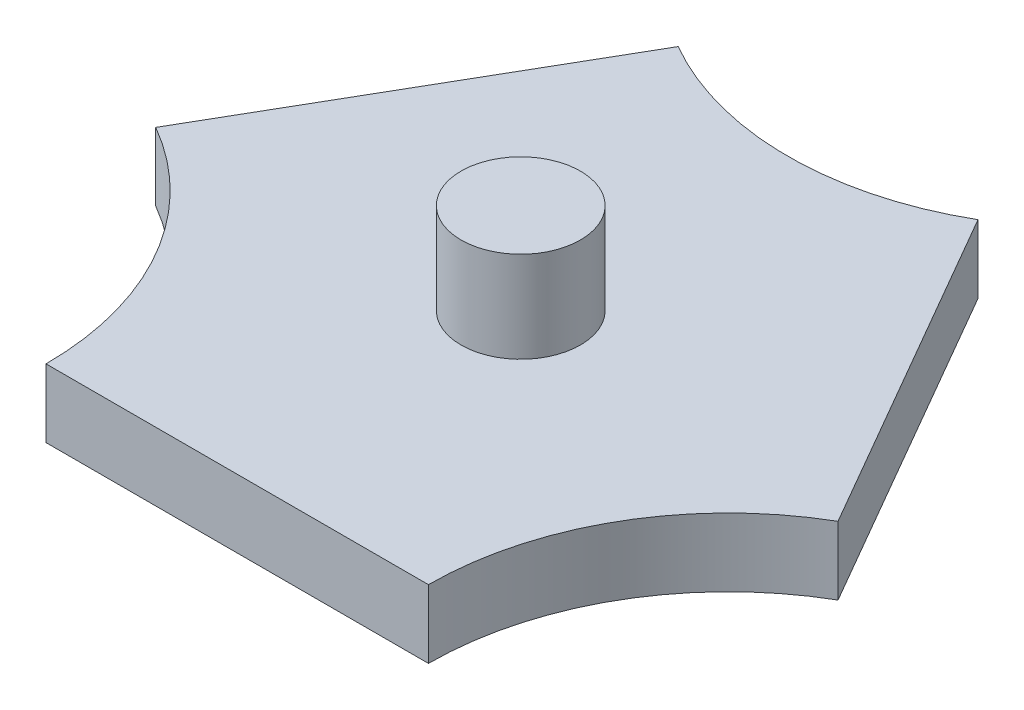
SolidWorks part; units mm, degrees
ref_plane "Front Plane" through (0, 0, 0) normal (0, 0, 1) x (1, 0, 0)
ref_plane "Top Plane" through (0, 0, 0) normal (0, 1, 0) x (1, 0, 0)
ref_plane "Right Plane" through (0, 0, 0) normal (1, 0, 0) x (0, 0, -1)
sketch "Sketch1" plane through (0, 0, 0) normal (0, 1, 0) x (1, 0, 0)
  line L0 (0, 0) -> (43.1834, 0) construction
  line L1 (43.1834, 0) -> (21.5917, 37.3979) construction
  line L2 (21.5917, 37.3979) -> (0, 0) construction
  line L3 (6.5917, 11.4171) -> (15, 25.9808)
  line L4 (28.1834, 25.9808) -> (36.5917, 11.4171)
  line L5 (13.1834, 0) -> (30, 0)
  arc A0 (15, 25.9808) -> (28.1834, 25.9808) centre (21.5917, 37.3979) ccw
  arc A1 (36.5917, 11.4171) -> (30, 0) centre (43.1834, 0) ccw
  arc A2 (6.5917, 11.4171) -> (13.1834, 0) centre (0, 0) cw
  point P9 (10.7958, 18.6989)
  point P10 (10.7958, 18.6989)
  point P11 (32.3875, 18.6989)
  point P12 (32.3875, 18.6989)
  point P13 (21.5917, 0)
  point P15 (21.5917, 0)
  dimension "D2" = 13.1834
  dimension "D1" = 30
  dimension "D3" = 16.8166
extrude "Boss-Extrude1" add sketch "Sketch1" along normal blind 3 contours A0 L4 A1 L5 A2 L3
sketch "Sketch2" plane through (0, 3, 0) normal (0, 1, 0) x (1, 0, 0)
  line L0 (21.5917, 0) -> (21.5917, 12.466) construction
  line L1 (13.1834, 0) -> (30, 0) construction
  line L2 (10.7958, 18.6989) -> (21.5917, 12.466) construction
  line L3 (6.5917, 11.4171) -> (15, 25.9808) construction
  line L4 (21.5917, 12.466) -> (32.3875, 18.6989) construction
  line L5 (28.1834, 25.9808) -> (36.5917, 11.4171) construction
  circle A0 centre (21.5917, 12.466) radius 2.625
  dimension "D1" = 5.25
extrude "Boss-Extrude2" add sketch "Sketch2" along normal blind 4
